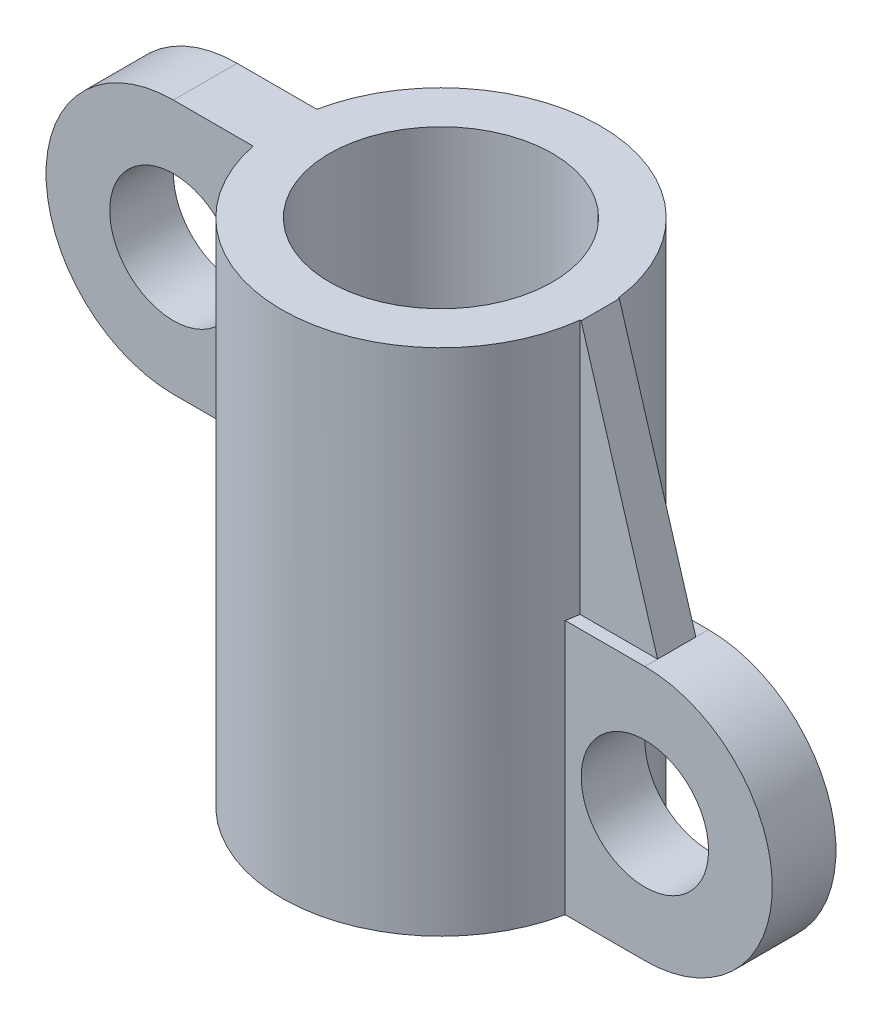
SolidWorks part; units mm, degrees
ref_plane "Front Plane" through (0, 0, 0) normal (0, 0, 1) x (1, 0, 0)
ref_plane "Top Plane" through (0, 0, 0) normal (0, 1, 0) x (1, 0, 0)
ref_plane "Right Plane" through (0, 0, 0) normal (1, 0, 0) x (0, 0, -1)
sketch "Sketch1" plane through (0, 0, 0) normal (0, 1, 0) x (1, 0, 0)
  circle A0 centre (0, 0) radius 25
  dimension "D1" = 50
extrude "Boss-Extrude1" add sketch "Sketch1" along normal blind 80
sketch "Sketch2" plane through (0, 0, 0) normal (0, 0, 1) x (1, 0, 0)
  line L0 (0, 80) -> (-37, 80)
  line L1 (25, 80) -> (-25, 80) construction
  line L2 (-37, 40) -> (0, 40)
  line L3 (0, 40) -> (0, 80)
  arc A0 (-37, 80) -> (-37, 40) centre (-37, 60) ccw
  circle A1 centre (-37, 60) radius 10
  dimension "D2" = 20
  dimension "D5" = 20
  dimension "D1" = 37
  dimension "D3" = 37
  dimension "D4" = 40
extrude "Boss-Extrude2" add sketch "Sketch2" along normal blind 5 and the other way blind 5
sketch "Sketch3" plane through (0, 0, 0) normal (0, 0, 1) x (1, 0, 0)
  line L0 (0, 0) -> (37, 0)
  line L1 (37, 40) -> (0, 40)
  line L2 (0, 40) -> (0, 0)
  arc A0 (37, 0) -> (37, 40) centre (37, 20) ccw
  circle A1 centre (37, 20) radius 10
  dimension "D2" = 20
  dimension "D5" = 20
  dimension "D1" = 37
  dimension "D3" = 37
  dimension "D4" = 40
extrude "Boss-Extrude3" add sketch "Sketch3" along normal blind 5 and the other way blind 5
sketch "Sketch4" plane through (0, 0, 0) normal (0, 0, 1) x (1, 0, 0)
  line L0 (25, 80) -> (37, 40)
  line L1 (25, 80) -> (0.2526, 80)
  line L2 (25, 80) -> (-24.4949, 80) construction
  line L3 (37, 40) -> (0.2526, 40)
  line L4 (0.2526, 40) -> (0.2526, 80)
  dimension "D1" = 40
  dimension "D2" = 24.7474
  dimension "D3" = 36.7474
  dimension "D4" = 40
extrude "Boss-Extrude4" add sketch "Sketch4" along normal blind 3 and the other way blind 3
sketch "Sketch5" plane through (0, 0, 0) normal (0, 1, 0) x (1, 0, 0)
  line L1 (24.8193, 3) -> (-58.519, 3)
  line L2 (24.8193, 3) -> (24.8193, -3)
  line L3 (24.8193, -3) -> (-58.519, -3)
  line L4 (-58.519, 3) -> (-58.519, -3)
  circle A0 centre (0, 0) radius 17.5
  dimension "D5" = 35
  dimension "D1" = 83.3383
  dimension "D2" = 6
  dimension "D3" = 6
  dimension "D4" = 83.3383
extrude "Cut-Extrude10" cut sketch "Sketch5" along normal blind 80 contours A0
